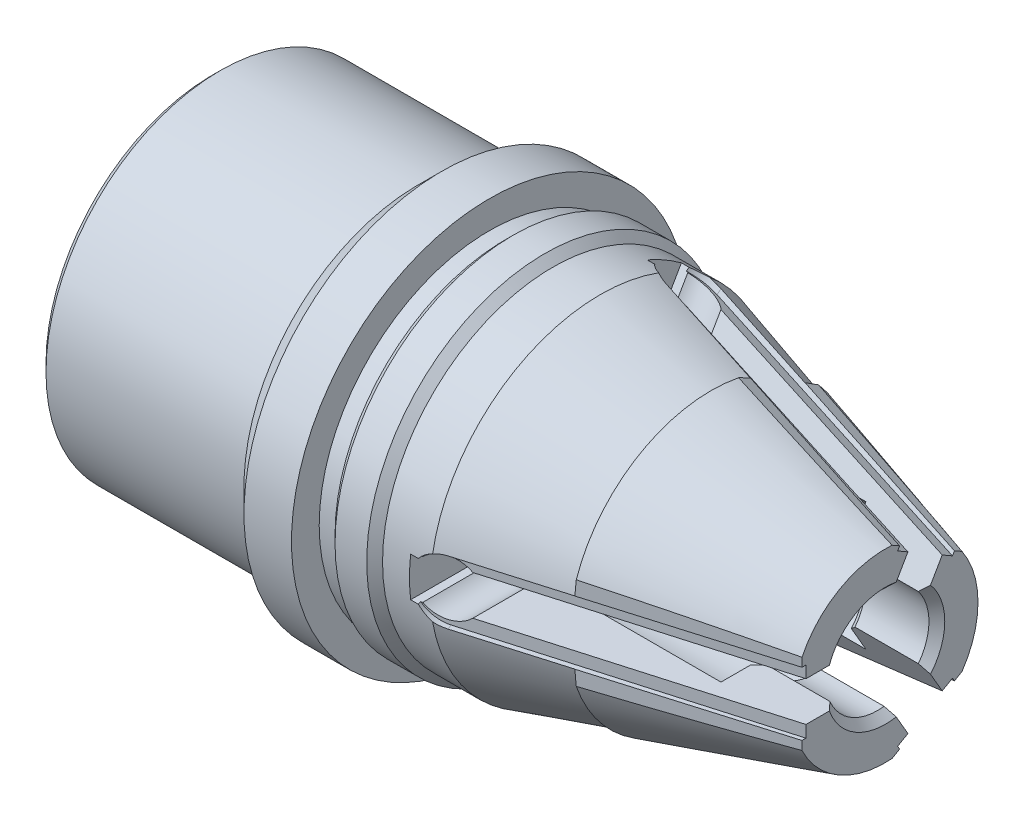
SolidWorks part; units mm, degrees
material "1.1191 (C45E)"
ref_plane "Plan de face" through (0, 0, 0) normal (0, 0, 1) x (1, 0, 0)
ref_plane "Plan de dessus" through (0, 0, 0) normal (0, 1, 0) x (1, 0, 0)
ref_plane "Plan de droite" through (0, 0, 0) normal (1, 0, 0) x (0, 0, -1)
sketch "Esquisse1" plane through (0, 0, 0) normal (0, 0, 1) x (1, 0, 0)
  line L0 (0, 0) -> (-59.9722, 0) construction
  line L1 (0, 0) -> (0, 22)
  line L2 (0, 22) -> (26, 22)
  line L3 (26, 22) -> (29, 25)
  line L4 (29, 25) -> (35, 25)
  line L5 (35, 25) -> (35, 21.5)
  line L6 (35, 21.5) -> (37, 21.5)
  line L7 (37, 21.5) -> (37, 22.5)
  line L8 (37, 22.5) -> (43, 22.5)
  line L9 (43, 22.5) -> (43, 21.5)
  line L10 (43, 21.5) -> (49, 21.5)
  line L11 (49, 21.5) -> (62.8622, 17.5251)
  line L12 (62.8622, 17.5251) -> (63, 18.0057)
  line L13 (63, 18.0057) -> (85, 11.6973)
  line L14 (85, 11.6973) -> (85, 0)
  line L15 (85, 0) -> (0, 0)
  dimension "D1" = 44
  dimension "D2" = 35
  dimension "D3" = 50
  dimension "D4" = 45
  dimension "D5" = 2
  dimension "D6" = 14
  dimension "D7" = 8
  dimension "D8" = 45
  dimension "D9" = 16
  dimension "D10" = 43
  dimension "D11" = 6
  dimension "D12" = 36
  dimension "D13" = 0.5
  dimension "D14" = 22
revolve "Révolution1" add sketch "Esquisse1" angle 360 about L0
cosmetic thread "Représentation de filetage2" parameters "D2"=43
sketch "Esquisse2" plane through (0, 0, 0) normal (0, 0, 1) x (1, 0, 0)
  line L0 (0, 0) -> (-18.803, 0) construction
  line L1 (0, 0) -> (85, 0)
  line L2 (85, -11.6973) -> (85, 11.6973) construction
  line L3 (85, 0) -> (85, 6.5)
  line L4 (85, 6.5) -> (75, 6.5)
  line L5 (75, 6.5) -> (75, 11.05)
  line L6 (75, 11.05) -> (44, 11.05)
  line L7 (44, 11.05) -> (44, 13.75)
  line L8 (44, 13.75) -> (35.05, 13.75)
  line L9 (35.05, 13.75) -> (35.05, 14.25)
  line L10 (35.05, 14.25) -> (25.05, 14.25)
  line L11 (25.05, 14.25) -> (25.05, 13.75)
  line L12 (25.05, 13.75) -> (16.1, 13.75)
  line L13 (16.1, 13.75) -> (16.1, 17.5)
  line L14 (16.1, 17.5) -> (0, 17.5)
  line L15 (0, 22) -> (0, -22) construction
  line L16 (0, 17.5) -> (0, 0)
  dimension "D1" = 35
  dimension "D2" = 27.5
  dimension "D3" = 0.5
  dimension "D4" = 44
  dimension "D5" = 10
  dimension "D6" = 13
  dimension "D7" = 22.1
  dimension "D8" = 10
  dimension "D9" = 16.1
revolve "Enlèvement de matière-Révolution1" cut sketch "Esquisse2" angle 360 about L0
cosmetic thread "Représentation de filetage1" parameters "D1"=8, "D2"=37
sketch "Esquisse3" plane through (0, 0, 0) normal (0, 0, 1) x (1, 0, 0)
  line L0 (85, -11.6973) -> (85, 11.6973) construction
  line L1 (46.4, 2.5) -> (47.4505, 2.5)
  line L2 (46.4, 2.5) -> (46.4, -2.5)
  line L3 (46.4, -2.5) -> (47.4505, -2.5)
  line L4 (85, 2.5) -> (85, -2.5)
  line L5 (46.4, 0) -> (0, 0) construction
  line L6 (52.3495, -2.5) -> (85, -2.5)
  line L7 (52.3495, 2.5) -> (85, 2.5)
  arc A0 (47.4505, -2.5) -> (52.3495, -2.5) centre (49.9, 0) ccw
  arc A1 (52.3495, 2.5) -> (47.4505, 2.5) centre (49.9, 0) ccw
  dimension "D3" = 7
  dimension "D1" = 5
  dimension "D2" = 38.6
extrude "Enlèv. mat.-Extru.1" cut sketch "Esquisse3" along normal through all
sketch "Esquisse4" plane through (85, 0, 0) normal (1, 0, 0) x (0, 0, -1)
  line L0 (-10.027, 0) -> (0, 0) construction
  line L1 (-18.027, 4) -> (-10.027, 4)
  line L2 (-18.027, 4) -> (-18.027, -4)
  line L3 (-18.027, -4) -> (-10.027, -4)
  line L4 (-10.027, 4) -> (-10.027, -4)
  dimension "D1" = 1.4
  dimension "D2" = 8
sketch "Esquisse5" plane through (0, 0, 0) normal (0, 1, 0) x (1, 0, 0)
  line L0 (85, -10.027) -> (51, -19.8349)
  line L2 (0, 0) -> (85, 0.1351) construction
  line L3 (0, 22) -> (0, -22) construction
  line L4 (85, -11.427) -> (85, 11.6973) construction
  dimension "D1" = 34
  dimension "D2" = 16
sweep "Enlèvement de matière-Balayage1" cut profiles "Esquisse4" path "Esquisse5"
sketch "Esquisse6" plane through (9.2, 0, 31.8928) normal (0.2772, 0, 0.9608) x (0.9608, 0, -0.2772)
  line L0 (43.3088, 4) -> (55.6703, 4) construction
  line L1 (55.6703, -4) -> (43.3088, -4) construction
  line L2 (38.7168, -2.5) -> (38.7168, 2.5)
  line L3 (38.7168, -2.5) -> (38.7168, 2.5) construction
  line L4 (42.7168, 4) -> (44.9089, 4)
  line L5 (44.9089, 4) -> (44.9089, -4)
  line L6 (43.5044, -4) -> (78.8907, -4) construction
  line L7 (44.9089, -4) -> (42.7168, -4)
  arc A0 (42.7168, 4) -> (42.7168, -4) centre (42.7168, 0) ccw
extrude "Enlèv. mat.-Extru.2" cut sketch "Esquisse6" along normal through all
sketch "Esquisse7" plane through (0, 0, 0) normal (0, 1, 0) x (1, 0, 0)
  line L0 (49, -21.1783) -> (85, -10.527)
  line L1 (85, -10.9921) -> (85, 11.6973) construction
  line L2 (85, -10.527) -> (85, -14.527)
  line L3 (85, -14.527) -> (49, -25.1783)
  line L4 (49, -25.1783) -> (49, -21.1783)
  dimension "D1" = 0.5
  dimension "D2" = 4
extrude "Enlèv. mat.-Extru.3" cut sketch "Esquisse7" against normal through all and the other way through all
chamfer "Chanfrein1" distance 1 angle 45 6 edges at (44, 0, -11.05) (16.1, 0, -13.75) (75, 0, -6.5) (85, 0, -6.5) (0, 0, -17.5) (0, 0, -22)
chamfer "Chanfrein2" distance 1 angle 45 2 edges at (43, 0, -22.5) (37, 0, -22.5)
pattern_circular "Répétition circulaire1" count 3 over 360 about axis through (0, 0, 0) along (-1, 0, 0) of "Enlèv. mat.-Extru.1", "Enlèvement de matière-Balayage1", "Enlèv. mat.-Extru.2", "Enlèv. mat.-Extru.3"
